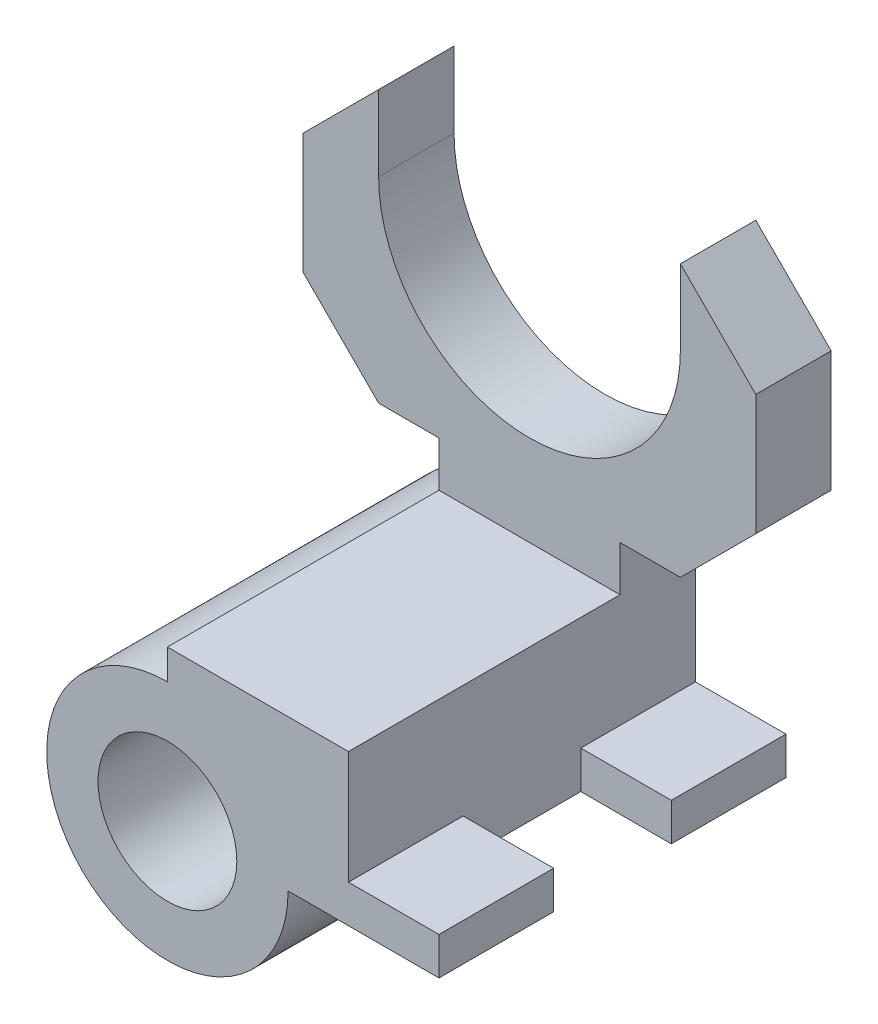
SolidWorks part; units mm, degrees
note: The reader was unsure of these and kept them because the rebuilt part matched: shared geometry of "Sketch1<3>", "Sketch1<4>", "Sketch1<5>".
ref_plane "Front Plane" through (0, 0, 0) normal (0, 0, 1) x (1, 0, 0)
ref_plane "Top Plane" through (0, 0, 0) normal (0, 1, 0) x (1, 0, 0)
ref_plane "Right Plane" through (0, 0, 0) normal (1, 0, 0) x (0, 0, -1)
sketch "Sketch1" plane through (0, 0, 0) normal (0, 0, 1) x (1, 0, 0)
  line L0 (-15.24, 25.4) -> (-15.24, 66.04) construction
  line L1 (0, 0) -> (-10.16, 0)
  line L2 (0, 0) -> (0, 25.4)
  line L3 (0, 25.4) -> (-30.48, 25.4)
  line L4 (-30.48, 20.32) -> (-30.48, 25.4)
  line L5 (0, 6.35) -> (15.24, 6.35)
  line L6 (0, 6.35) -> (0, 0)
  line L7 (0, 0) -> (15.24, 0)
  line L8 (15.24, 6.35) -> (15.24, 0)
  line L9 (-30.48, 25.4) -> (-30.48, 33.02)
  line L10 (-30.48, 33.02) -> (-40.64, 33.02)
  line L11 (-40.64, 33.02) -> (-53.34, 45.72)
  line L12 (-53.34, 45.72) -> (-53.34, 66.04)
  line L13 (-53.34, 66.04) -> (-40.64, 78.74)
  line L14 (-40.64, 66.04) -> (-40.64, 78.74)
  line L15 (0, 33.02) -> (10.16, 33.02)
  line L16 (0, 25.4) -> (0, 33.02)
  line L17 (10.16, 66.04) -> (10.16, 78.74)
  line L18 (22.86, 66.04) -> (10.16, 78.74)
  line L19 (22.86, 45.72) -> (22.86, 66.04)
  line L20 (10.16, 33.02) -> (22.86, 45.72)
  circle A0 centre (-30.48, 0) radius 11.684
  arc A1 (-30.48, 20.32) -> (-10.16, 0) centre (-30.48, 0) ccw
  arc A2 (-40.64, 66.04) -> (10.16, 66.04) centre (-15.24, 66.04) ccw
  dimension "D5" = 23.368
  dimension "D6" = 40.64
  dimension "D16" = 15.24
  dimension "D1" = 30.48
  dimension "D2" = 25.4
  dimension "D3" = 6.35
  dimension "D4" = 15.24
  dimension "D7" = 20.32
  dimension "D8" = 10.16
  dimension "D9" = 40.64
  dimension "D10" = 135
  dimension "D11" = 33.02
  dimension "D12" = 20.32
  dimension "D13" = 135
  dimension "D14" = 12.7
  dimension "D15" = 25.4
extrude "Boss-Extrude1" add sketch "Sketch1" along normal blind 12.7 contours L3 L0 A2 L14 L13 L12 L11 L10 L9 | L0 L3 L16 L15 L20 L19 L18 L17 A2 | L4 A1 L1 L2 L3 A0
extrude "Boss-Extrude2" add sketch "Sketch1<3>" along normal blind 45.72 from surface at 12.7 contours L4 A1 L1 L2 L3 A0 starting at face at (-16.5366, 41.0368, 12.7)
sketch "Sketch1<3>" plane through (0, 0, 0) normal (0, 0, 1) x (1, 0, 0) same geometry as "Sketch1"
extrude "Boss-Extrude3" add sketch "Sketch1<4>" along normal blind 19.304 contours L8 L5 L2 L7
sketch "Sketch1<4>" plane through (0, 0, 0) normal (0, 0, 1) x (1, 0, 0) same geometry as "Sketch1"
extrude "Boss-Extrude5" add sketch "Sketch1<5>" against normal blind 19.304 from vertex contours L8 L5 L2 L7 starting at point (0, 0, 58.42)
sketch "Sketch1<5>" plane through (0, 0, 0) normal (0, 0, 1) x (1, 0, 0) same geometry as "Sketch1"
